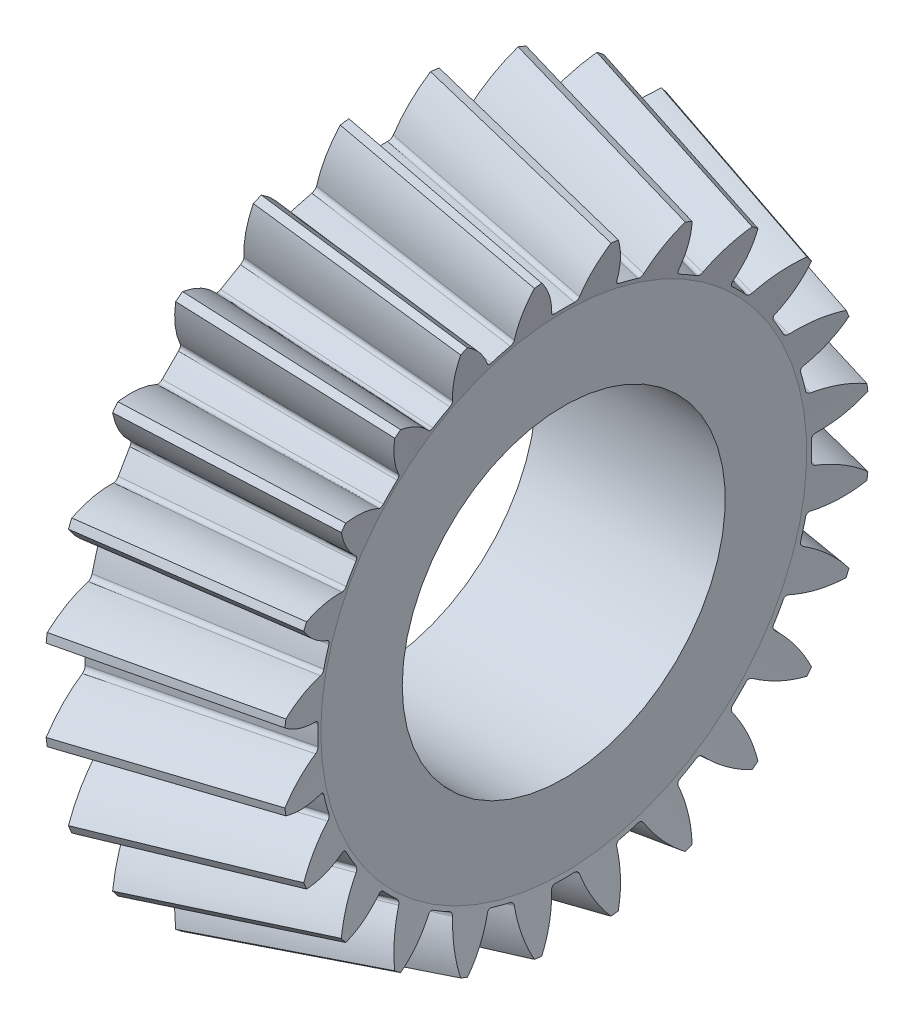
SolidWorks part; units mm, degrees
revolve "Base-Revolve" add sketch "BasProSke" angle 360 about L0 other way angle 7.5
sketch "BasProSke" plane through (0, 0, 0) normal (0, 1, 0) x (1, 0, 0)
  line L0 (-10, 0) -> (60, 0) construction
  line L1 (0, 0) -> (0, 22.1634)
  line L2 (0, 0) -> (14.6217, 0)
  line L3 (14.6217, 0) -> (14.6217, 18.8038)
  line L4 (96.4592, 0) -> (-30.3036, 31.6907) construction
  line L5 (0, 22.1634) -> (1.1534, 26.777)
  line L6 (96.4592, 0) -> (-39.3322, 38.1518) construction
  line L7 (96.4592, 0) -> (0, 22.1634) construction
  line L8 (1.1534, 26.777) -> (15.6003, 22.718)
  line L9 (15.6003, 22.718) -> (14.6217, 18.8038)
  line L10 (0.4592, 24) -> (-11.5252, 24) construction
  dimension "Addendum" = 2.8625
  dimension "Pitch_rad" = 24
  dimension "Dedendum_plus" = 1.8931
  dimension "Pitch_ang" = 14.036
  dimension "D1" = 44.3268
  dimension "D2" = 96.4592
  dimension "D3" = 98.9545
  dimension "D4" = 1.657
ref_plane "Plane1" through (0, 0, 0) normal (0, 0, 1) x (1, 0, 0)
ref_plane "Plane2" through (0, 0, 0) normal (0, 1, 0) x (1, 0, 0)
ref_plane "Plane3" through (0, 0, 0) normal (1, 0, 0) x (0, 0, -1)
sketch "HoldingSke" plane through (0, 0, 0) normal (0, 1, 0) x (1, 0, 0)
  line L0 (0, 0) -> (0.4568, -0.2034)
  line L1 (-15, 0) -> (100, 0) construction
  line L2 (0, 0) -> (102.0196, 90.0878)
  line L3 (0, 0) -> (-11.863, 4.5341)
  line L4 (0, 0) -> (7.8894, 3.5126)
  line L5 (0, 0) -> (-60.9019, -22.7146)
  line L6 (0, 0) -> (-10.5278, -7.1032)
  line L7 (102.0196, 90.0878) -> (198.0234, 99.4501)
  line L8 (-76.2, 2) -> (-72.9, 2)
  line L9 (-67.7845, 28.3722) -> (-49.3413, 33.142)
  line L10 (-76.2, 71.12) -> (104.1128, 71.12)
  line L11 (0, 0) -> (-15, 0)
  line L12 (-76.2, 101.6) -> (-76.133, 101.6)
  line L13 (24.9733, 27.94) -> (52.9474, 28.6389)
  line L14 (24.9733, 27.94) -> (24.9743, 27.94)
  line L15 (24.9733, 27.94) -> (100.412, 28.9364)
  line L16 (102.0196, 90.0878) -> (88.5242, -38.3122)
  circle A0 centre (0, 0) radius 12.5
  circle A1 centre (0, 0) radius 12.5
  circle A2 centre (0, 0) radius 12.5
  circle A3 centre (0, 0) radius 12.5
  dimension "MHD" = 25
  dimension "Hub_dia" = 25
  dimension "Bore" = 25
  dimension "MBD" = 25
  dimension "Num_teeth" = 24
  dimension "Pitch" = 0.5
  dimension "Mounting_dist" = 65
  dimension "Show_teeth" = 24
  dimension "Thickness" = 12.7
  dimension "OAL" = 96.4592
  dimension "T_dim" = 3.3
  dimension "Ap" = 14.5
  dimension "H" = 19.05
  dimension "Pitch_radius" = 180.3128
  dimension "Backlash" = 0.067
  dimension "Addendum_fac" = 1.431
  dimension "Dedendum_fac" = 0.757
  dimension "Clearance_fac" = 0.188
  dimension "Dedendum_add" = 0.001
  dimension "Mating_teeth" = 96
  dimension "MnMD" = 96.4592
  dimension "Module" = 2
ref_plane "ToothPln" through (0.5767, 24.4702, 0) normal (-0.9701, 0.2425, 0) x (0, 0, -1)
ref_plane "ToothPln2" through (90.7851, -22.6963, 0) normal (-0.9701, 0.2425, 0) x (0, 0, 1)
sketch "TooCutSke" plane through (0.5767, 24.4702, 0) normal (-0.9701, 0.2425, 0) x (0, 0, -1)
  line L2 (0, 24.4847) -> (215.0692, -1609.1277) construction
  line L3 (0, 24.4847) -> (118.622, -1747.3588) construction
  line L4 (0, -15.621) -> (0, 105.791) construction
  line L6 (-24.765, -2.3778) -> (21.082, -2.3778) construction
  line L7 (3.1326, 0.69) -> (1.5999, 0.5874) construction
  arc A0 (-3.5787, -2.6803) -> (3.5787, -2.6803) centre (0, 24.4847) ccw
  arc A1 (-0.8875, 2.0167) -> (0.8875, 2.0167) centre (0, 24.4847) ccw
  circle A2 centre (0, 24.4847) radius 24 construction
  circle A3 centre (0, 24.4847) radius 23.2355 construction
  arc A4 (1.2703, 1.7226) -> (0.8875, 2.0167) centre (0.9024, 1.64) ccw
  arc A5 (1.2703, 1.7226) -> (3.5787, -2.6803) centre (10.6368, 3.8268) ccw
  arc A6 (-3.5787, -2.6803) -> (-1.2703, 1.7226) centre (-10.6368, 3.8268) ccw
  arc A7 (-0.8875, 2.0167) -> (-1.2703, 1.7226) centre (-0.9024, 1.64) ccw
  ellipse E0 centre (0, 23.5997) end of major axis (26.777, 23.5997) minor radius 25.9775 construction
sketch "TooCutSke2" plane through (90.7851, -22.6963, 0) normal (-0.9701, 0.2425, 0) x (0, 0, 1)
  line L0 (0, 0) -> (0, 68.072) construction
  line L2 (21.082, 21.5017) -> (-20.32, 21.5017) construction
  circle A0 centre (0, 23.3948) radius 0.0127
  ellipse E1 centre (0, 0) end of major axis (-22.1634, 0) minor radius 21.5017 construction
  dimension "Dedendum_plus" = 1.8931
loft "ToothCut" cut profiles "TooCutSke2", "TooCutSke"
pattern_circular "TeethCuts" count 24 every 15 about axis through (-10, 0, 0) along (1, 0, 0) of "ToothCut"
sketch "HubSke" plane through (0, 0, 0) normal (-1, 0, 0) x (0, 0, 1)
  circle A0 centre (0, 0) radius 12.5
  dimension "Diameter" = 25
extrude "Hub" add sketch "HubSke" along normal blind 0.0001
sketch "BorSke" plane through (0, 0, 0) normal (1, 0, 0) x (0, 0, -1)
  circle A0 centre (0, 0) radius 12.5
  dimension "Diameter" = 25
extrude "Bore" cut sketch "BorSke" along normal mid plane 192.9184
sketch "KeySke" plane through (0, 0, 0) normal (1, 0, 0) x (0, 0, -1)
  line L0 (-4, 0) -> (-4, 15.8)
  line L1 (-4, 15.8) -> (4, 15.8)
  line L2 (4, 15.8) -> (4, 0)
  line L3 (0, 0) -> (0, 34) construction
  line L4 (-4, 0) -> (4, 0)
  dimension "Offset" = 15.8
extrude "Keyway" [suppressed] cut sketch "KeySke" along normal mid plane 192.9184
pattern_circular "Keyway2" [suppressed] count 2 every 90 about axis through (-10, 0, 0) along (1, 0, 0) reverse direction yes
equation "' \"Module@HoldingSke\" = 6.35"
equation "' \"Num_teeth@HoldingSke\" = 12"
equation "' \"Mating_teeth@HoldingSke\" = 20"
equation "' \"Ap@HoldingSke\" =  20"
equation "' \"Ap@HoldingSke\" = 20"
equation "' \"Width@HoldingSke\" = 0.5 * 25.4"
equation "' \"Hub_dia@HoldingSke\"= 2 * 25.4"
equation "' \"Hub_dia@HoldingSke\" = 2 * 25.4"
equation "' \"Mounting_dist@HoldingSke\" = 3 * 25.4"
equation "' \"Bore@HoldingSke\" = 19"
equation "' \"T_dim@HoldingSke\" = 0.1 * 25.4"
equation "' \"Width@KeySke\" = 0.25 * 25.4"
equation "' \"Show_teeth@HoldingSke\" = 100"
equation "' \"Backlash@HoldingSke\" = 0.009 * 25.4"
equation "' \"Addendum_fac@HoldingSke\" = 1.0"
equation "' \"Dedendum_fac@HoldingSke\" = 1.188"
equation "' \"Dedendum_add@HoldingSke\" = 0.002 * 25.4"
equation "' \"Clearance_fac@HoldingSke\" = 0.188"
equation "\"Pitch@HoldingSke\" = 1 / \"Module@HoldingSke\""
equation "' \"Addendum_fac@HoldingSke\" = 0.54 + 0.46 / (\"Num_teeth@HoldingSke\" /  \"Mating_teeth@HoldingSke\" ) ^ 2"
equation " \"Addendum_fac@HoldingSke\" = 2 - (0.54 + 0.46 / (\"Mating_teeth@HoldingSke\" /  \"Num_teeth@HoldingSke\" ) ^ 2)"
equation "\"Dedendum_fac@HoldingSke\" = 2.188 - \"Addendum_fac@HoldingSke\""
equation "\"Pitch_rad@BasProSke\" = \"Num_teeth@HoldingSke\" / \"Pitch@HoldingSke\" / 2"
equation "\"Pitch_ang@BasProSke\" = atn(\"Num_teeth@HoldingSke\" / \"Mating_teeth@HoldingSke\") * (180 / 3.14159265)"
equation "\"Addendum@BasProSke\" = \"Addendum_fac@HoldingSke\" / \"Pitch@HoldingSke\""
equation "\"Dedendum_plus@BasProSke\" = (\"Dedendum_fac@HoldingSke\" / \"Pitch@HoldingSke\" + \"Dedendum_add@HoldingSke\") * 1.25"
equation "\"Face_wid@BasProSke\" = \"Width@HoldingSke\""
equation "\"Radius@TooCutSke\" = ((\"Num_teeth@HoldingSke\" + 2 * \"Addendum_fac@HoldingSke\") / \"Pitch@HoldingSke\" ) / 2"
equation "\"Overcut_dia@TooCutSke\" =  1.02 * (\"Num_teeth@HoldingSke\" + 2 * \"Addendum_fac@HoldingSke\") / \"Pitch@HoldingSke\""
equation "\"Pitch_dia@TooCutSke\" = \"Num_teeth@HoldingSke\" / \"Pitch@HoldingSke\""
equation "\"Base_dia@TooCutSke\" = \"Num_teeth@HoldingSke\" / \"Pitch@HoldingSke\" * cos((\"Ap@HoldingSke\"  * 3.14159265 / 180))"
equation "'  \"Root_dia@TooCutSke\" =  (\"Num_teeth@HoldingSke\" + 2) / \"Pitch@HoldingSke\" - 2 * (\"Addendum_fac@HoldingSke\" + \"Dedendum_fac@HoldingSke\") / \"Pitch@HoldingSke\" - \"Dedendum_add@HoldingSke\" * 2"
equation "'  \"Root_dia@TooCutSke\" = (\"Num_teeth@HoldingSke\" + 2) / \"Pitch@HoldingSke\" - 2 * (\"Addendum_fac@HoldingSke\" + \"Dedendum_fac@HoldingSke\") / \"Pitch@HoldingSke\" - \"Dedendum_add@HoldingSke\" * 2"
equation "\"Root_dia@TooCutSke\" =  \"Num_teeth@HoldingSke\" / \"Pitch@HoldingSke\" -  2 * \"Dedendum_fac@HoldingSke\" / \"Pitch@HoldingSke\" - \"Dedendum_add@HoldingSke\" * 2"
equation "\"Half_ang@TooCutSke\" = 180 / \"Num_teeth@HoldingSke\""
equation "\"Half_CT@TooCutSke\" = \"Num_teeth@HoldingSke\" / \"Pitch@HoldingSke\" * sin((3.14159265 / 2 / \"Num_teeth@HoldingSke\")) / 2 - 2 * \"Backlash@HoldingSke\" / 4"
equation "\"Flank_rad@TooCutSke\" = \"Num_teeth@HoldingSke\" / \"Pitch@HoldingSke\" / 5"
equation "\"Root_fillet@TooCutSke\" = \"Clearance_fac@HoldingSke\" / \"Pitch@HoldingSke\" + \"Dedendum_add@HoldingSke\""
equation "\"Offset@ToothPln2\"  = \"Num_teeth@HoldingSke\" / \"Pitch@HoldingSke\" / 2 / sin(atn(\"Num_teeth@HoldingSke\" / \"Mating_teeth@HoldingSke\"))"
equation "\"Dedendum_plus@TooCutSke2\" = \"Dedendum_plus@BasProSke\""
equation "\"MHD@HoldingSke\" = \"Num_teeth@HoldingSke\" / \"Pitch@HoldingSke\" - 2 * \"Dedendum_plus@BasProSke\" * cos(atn(\"Num_teeth@HoldingSke\" / \"Mating_teeth@HoldingSke\"))"
equation "\"MBD@HoldingSke\" = \"Num_teeth@HoldingSke\" / \"Pitch@HoldingSke\" - 2 * \"Dedendum_plus@BasProSke\" * cos(atn(\"Num_teeth@HoldingSke\" / \"Mating_teeth@HoldingSke\")) - 0.002 * 25.4"
equation "\"MnMD@HoldingSke\" =  \"Num_teeth@HoldingSke\" / \"Pitch@HoldingSke\" / 2 / (\"Num_teeth@HoldingSke\" / \"Mating_teeth@HoldingSke\") + \"Dedendum_plus@BasProSke\" * sin(atn(\"Num_teeth@HoldingSke\" / \"Mating_teeth@HoldingSke\"))"
equation "\"OAL@HoldingSke\" = \"MnMD@HoldingSke\""
equation "\"MHD@HoldingSke\" = ((sgn( \"MHD@HoldingSke\" - \"Hub_dia@HoldingSke\" )-1)*( \"MHD@HoldingSke\" - \"Hub_dia@HoldingSke\" ))/-2+ \"Hub_dia@HoldingSke\""
equation "\"MBD@HoldingSke\" = ((sgn( \"MBD@HoldingSke\" - \"Bore@HoldingSke\" )-1)*( \"MBD@HoldingSke\" - \"Bore@HoldingSke\" ))/-2+ \"Bore@HoldingSke\""
equation "\"Face_wid@BasProSke\" = ((sgn( \"Face_wid@BasProSke\" - \"Offset@ToothPln2\" * 0.9)-1)*( \"Face_wid@BasProSke\" - \"Offset@ToothPln2\" * 0.9))/-2+ \"Offset@ToothPln2\" * 0.9"
equation "\"OAL@HoldingSke\" = ((sgn( \"OAL@HoldingSke\" - \"Mounting_dist@HoldingSke\" )+1)*( \"OAL@HoldingSke\" - \"Mounting_dist@HoldingSke\" ))/2 + \"Mounting_dist@HoldingSke\" + 0.000002 * 25.4"
equation "\"Num_teeth@TeethCuts\" = int( \"Show_teeth@HoldingSke\" ) + 1"
equation "\"Num_teeth@TeethCuts\" = ((sgn( \"Num_teeth@TeethCuts\" - \"Num_teeth@HoldingSke\" )-1)*( \"Num_teeth@TeethCuts\" - \"Num_teeth@HoldingSke\" ))/-2+ \"Num_teeth@HoldingSke\""
equation "\"Num_teeth@TeethCuts\" = ((sgn( \"Num_teeth@TeethCuts\" - 2.0)+1)*( \"Num_teeth@TeethCuts\" - 2.0))/2 +2.0"
equation "\"Angle@TeethCuts\" = 360.0 / \"Num_teeth@HoldingSke\""
equation "\"Diameter@HubSke\" = \"MHD@HoldingSke\""
equation "\"Length@Hub\" = \"OAL@HoldingSke\" - \"MnMD@HoldingSke\" + 0.000002 * 25.4"
equation "\"Diameter@BorSke\" = \"MBD@HoldingSke\""
equation "\"D1@Bore\" = \"OAL@HoldingSke\" * 2.0"
equation "\"D1@Keyway\" = \"OAL@HoldingSke\" * 2.0"
equation "\"Offset@KeySke\" = \"T_dim@HoldingSke\" + \"MBD@HoldingSke\" / 2.0"
